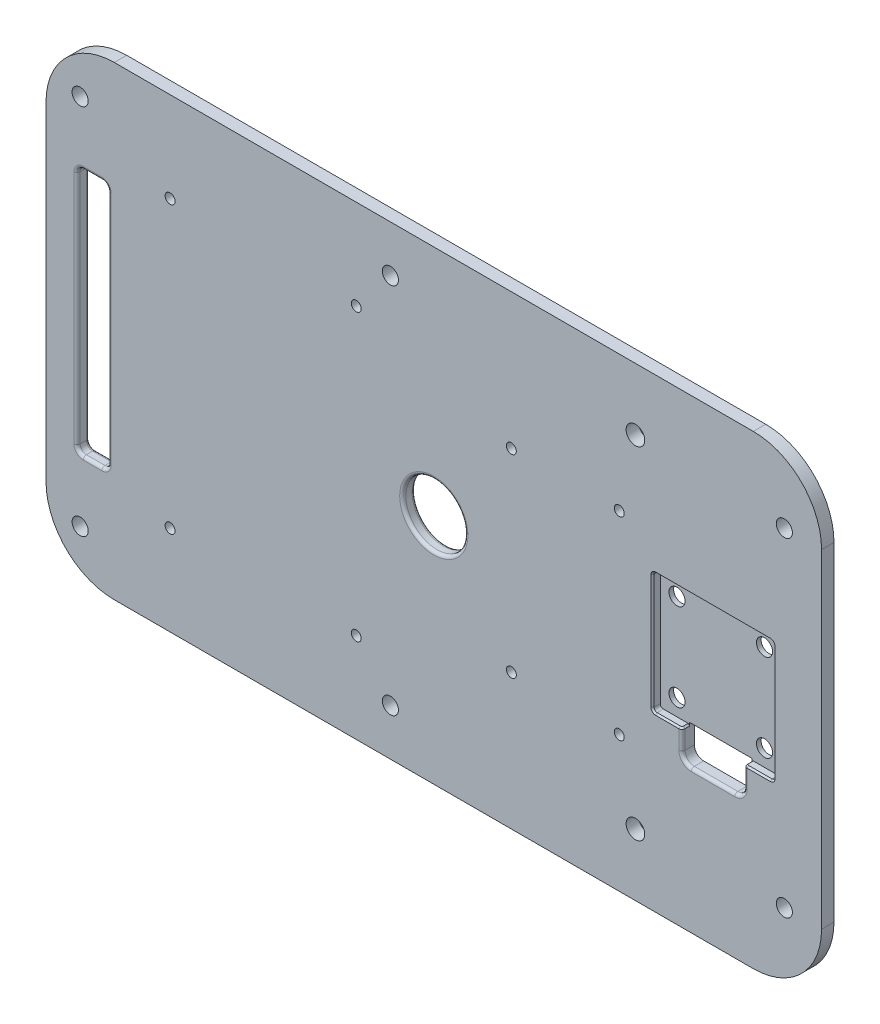
SolidWorks part; units mm, degrees
ref_plane "前视基准面" through (0, 0, 0) normal (0, 0, 1) x (1, 0, 0)
ref_plane "上视基准面" through (0, 0, 0) normal (0, 1, 0) x (1, 0, 0)
ref_plane "右视基准面" through (0, 0, 0) normal (1, 0, 0) x (0, 0, -1)
other "Configuration Table"
sketch "草图1" plane through (0, 0, 0) normal (0, 0, 1) x (1, 0, 0)
  line L0 (-1113.7626, 0) -> (48886.2374, 0) construction
  line L1 (-103, -75) -> (103, -75)
  line L2 (-125, -53) -> (-125, 53)
  line L3 (-103, 75) -> (103, 75)
  line L4 (125, -53) -> (125, 53)
  line L5 (-125, -75) -> (125, 75) construction
  line L6 (-125, 75) -> (125, -75) construction
  line L7 (-64, -1009.8705) -> (-64, 48990.1295) construction
  line L8 (-55, -1000) -> (-55, 49000) construction
  line L9 (-113, -40) -> (-107, -40)
  line L10 (-115, -38) -> (-115, 38)
  line L11 (-113, 40) -> (-107, 40)
  line L12 (-105, -38) -> (-105, 38)
  line L13 (-115, -40) -> (-105, 40) construction
  line L14 (-115, 40) -> (-105, -40) construction
  line L16 (-89, -50) -> (-21, -50) construction
  line L17 (-89, -50) -> (-89, 50) construction
  line L18 (-89, 50) -> (-21, 50) construction
  line L19 (-21, -50) -> (-21, 50) construction
  line L20 (-89, -50) -> (-21, 50) construction
  line L21 (-89, 50) -> (-21, -50) construction
  line L22 (80, -29) -> (100, -29)
  line L23 (80, -29) -> (80, -19)
  line L24 (80, -19) -> (100, -19)
  line L25 (100, -29) -> (100, -19)
  line L26 (80, -29) -> (100, -19) construction
  line L27 (80, -19) -> (100, -29) construction
  arc A0 (103, 75) -> (125, 53) centre (103, 53) cw
  arc A1 (103, -75) -> (125, -53) centre (103, -53) ccw
  arc A2 (-103, -75) -> (-125, -53) centre (-103, -53) cw
  arc A3 (-125, 53) -> (-103, 75) centre (-103, 53) cw
  circle A4 centre (-114, 60) radius 2.6
  circle A5 centre (-114, -60) radius 2.6
  circle A6 centre (-14, -60) radius 2.6
  circle A7 centre (-14, 60) radius 2.6
  arc A8 (-107, -40) -> (-105, -38) centre (-107, -38) ccw
  arc A9 (-113, -40) -> (-115, -38) centre (-113, -38) cw
  arc A10 (-105, 38) -> (-107, 40) centre (-107, 38) ccw
  arc A11 (-115, 38) -> (-113, 40) centre (-113, 38) cw
  circle A12 centre (-85, 46) radius 1.6
  circle A13 centre (-25, 46) radius 1.6
  circle A14 centre (-25, -46) radius 1.6
  circle A15 centre (-85, -46) radius 1.6
  circle A16 centre (103, 53) radius 2.6 construction
  circle A17 centre (103, -53) radius 2.6 construction
  circle A18 centre (0, 0) radius 10
  circle A19 centre (65, -55) radius 3
  circle A20 centre (65, 55) radius 3
  circle A21 centre (113, 53) radius 2.6
  circle A22 centre (113, -53) radius 2.6
  point P0 (0, 0)
  point P30 (-110, 0)
  point P57 (-55, 0)
  point P62 (90, -29)
  point P63 (90, -24)
  dimension "D3" = 22
  dimension "D4" = 5.2
  dimension "D6" = 11
  dimension "D7" = 15
  dimension "D8" = 120
  dimension "D12" = 2
  dimension "D13" = 3.2
  dimension "D14" = 92
  dimension "D15" = 60
  dimension "D23" = 5.2
  dimension "D24" = 20
  dimension "D25" = 60
  dimension "D26" = 20
  dimension "D27" = 5.2
  dimension "D28" = 10
  dimension "D29" = 22
  dimension "D1" = 150
  dimension "D2" = 250
  dimension "D5" = 50
  dimension "D9" = 10
  dimension "D10" = 10
  dimension "D11" = 80
  dimension "D16" = 70
  dimension "D17" = 68
  dimension "D18" = 100
  dimension "D19" = 20
  dimension "D20" = 10
  dimension "D21" = 24
  dimension "D22" = 80
extrude "凸台-拉伸1" add sketch "草图1" along normal blind 4
sketch "草图2" plane through (0, 0, 4) normal (0, 0, 1) x (1, 0, 0)
  line L0 (-1000, 0) -> (49000, 0) construction
  line L1 (70.5, -19.5) -> (109.5, -19.5)
  line L2 (70.5, -19.5) -> (70.5, 19.5)
  line L3 (70.5, 19.5) -> (109.5, 19.5)
  line L4 (109.5, -19.5) -> (109.5, 19.5)
  line L5 (70.5, -19.5) -> (109.5, 19.5) construction
  line L6 (70.5, 19.5) -> (109.5, -19.5) construction
  line L7 (0, -1000) -> (0, 49000) construction
  point P0 (90, 0)
  dimension "D1" = 39
  dimension "D2" = 39
  dimension "D3" = 90
extrude "切除-拉伸1" cut sketch "草图2" against normal blind 2.5
fillet "圆角1" radius 3 2 edges at (80, -29, 2) (100, -29, 2)
fillet "圆角2" radius 1 9 edges at (90, -29, 4) (80.8787, -28.1213, 4) (80, -22.75, 4) (70.5, -19.5, 2.75) (109.5, -19.5, 2.75) (109.5, 19.5, 2.75) (70.5, 19.5, 2.75) (99.1213, -28.1213, 4) (100, -22.75, 4)
chamfer "倒角1" distance 0.5 angle 45 10 edges at (70.7929, -19.2071, 4) (109.2071, -19.2071, 4) (109.5, 0, 4) (109.2071, 19.2071, 4) (90, 19.5, 4) (70.7929, 19.2071, 4) (70.5, 0, 4) (104.75, -19.5, 4) (100, -19.5, 2.25) (100.2929, -19.5, 3.7071)
sketch "草图4" plane through (0, 0, 1.5) normal (0, 0, 1) x (1, 0, 0)
  line L0 (71.5, -18.5) -> (108.5, 18.5) construction
  line L1 (71.5, 18.5) -> (108.5, -18.5) construction
  line L2 (-920, 0) -> (49080, 0) construction
  line L3 (90, -1000) -> (90, 49000) construction
  circle A0 centre (75.9003, -14.0997) radius 2.6
  circle A2 centre (104.0997, -14.0997) radius 2.6
  circle A3 centre (104.0997, 14.0997) radius 2.6
  circle A12 centre (75.9003, 14.0997) radius 2.6
  point P4 (80, -20)
  point P19 (90, 0)
  dimension "D2" = 5.2
  dimension "D3" = 39.88
extrude "切除-拉伸2" cut sketch "草图4" against normal blind 2
fillet "圆角3" radius 1 18 edges at (-114.4142, 39.4142, 0) (-110, 40, 0) (-105.5858, 39.4142, 0) (-105, 0, 0) (-105.5858, -39.4142, 0) (-110, -40, 0) (-114.4142, -39.4142, 0) (-114.4142, 39.4142, 4) (-110, 40, 4) (-105.5858, 39.4142, 4) (-105, 0, 4) (-105.5858, -39.4142, 4) (-110, -40, 4) (-114.4142, -39.4142, 4) (10, 0, 0) (10, 0, 4) (-115, 0, 0) (-115, 0, 4)
sketch "草图5" plane through (0, 0, 4) normal (0, 0, 1) x (1, 0, 0)
  line L0 (-1000, 0) -> (49000, 0) construction
  line L1 (25, 31.24) -> (59.79, 31.24) construction
  line L2 (25, 31.24) -> (25, -31.24) construction
  line L3 (25, -31.24) -> (59.79, -31.24) construction
  line L4 (59.79, 31.24) -> (59.79, -31.24) construction
  circle A0 centre (25, 31.24) radius 1.6
  circle A1 centre (59.79, 31.24) radius 1.6
  circle A2 centre (59.79, -31.24) radius 1.6
  circle A3 centre (25, -31.24) radius 1.6
  dimension "D3" = 3.2
  dimension "D1" = 62.48
  dimension "D2" = 34.79
  dimension "D6" = 31.24
  dimension "D7" = 25
  dimension "D4" = 2
  dimension "D5" = 2
extrude "切除-拉伸3" cut sketch "草图5" against normal through all
